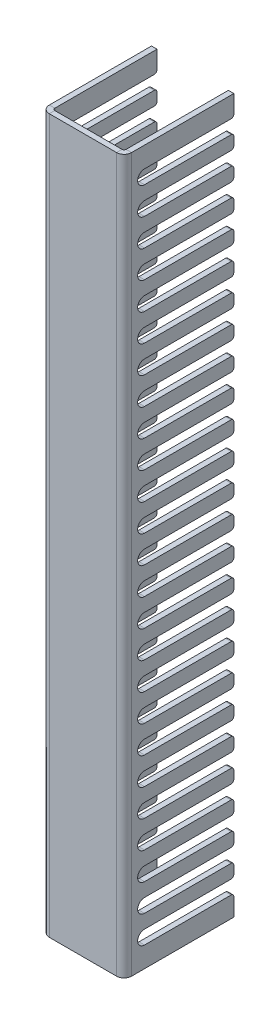
SolidWorks part; units mm, degrees
note: The reader was unsure of these and kept them because the rebuilt part matched: flange length of "边线-法兰1".
ref_plane "前视基准面" through (0, 0, 0) normal (0, 0, 1) x (1, 0, 0)
ref_plane "上视基准面" through (0, 0, 0) normal (0, 1, 0) x (1, 0, 0)
ref_plane "右视基准面" through (0, 0, 0) normal (1, 0, 0) x (0, 0, -1)
sketch "草图1" plane through (0, 0, 0) normal (0, 0, 1) x (1, 0, 0)
  line L1 (-18.0132, 35.6887) -> (11.9868, 35.6887)
  line L2 (-18.0132, 35.6887) -> (-18.0132, -224.3113)
  line L3 (-18.0132, -224.3113) -> (11.9868, -224.3113)
  line L4 (11.9868, 35.6887) -> (11.9868, -224.3113)
  dimension "D1" = 30
  dimension "D2" = 260
sheet metal parameters "钣金1" thickness 2 parameters "D1"=0.7366
base flange "基体-法兰1" sketch "草图1" thickness 2 reverse thickness direction no parameters "D1"=0.7366
edge flange "边线-法兰1" sketch "草图9" flange profiles "草图9", "草图10" flange angle 90 flange length 40 flange position material inside bend radius 0.7366 thickness 2 relief rectangular parameters "D6"=10, "D8"=1
sketch "草图9" plane through (11.9868, 0, -2) normal (1, 0, 0) x (0, -1, 0)
  line L2 (-35.6887, 0) -> (-35.6887, 38)
  line L3 (-35.6887, 38) -> (224.3113, 38)
  line L4 (224.3113, 38) -> (224.3113, 0)
  line L7 (224.3113, 0) -> (-35.6887, 0) construction
  line L8 (224.3113, 0) -> (-35.6887, 0)
sketch "草图10" plane through (-18.0132, 0, -2) normal (-1, 0, 0) x (0, 1, 0)
  line L0 (35.6887, 0) -> (-224.3113, 0) construction
  line L1 (35.6887, 0) -> (-224.3113, 0)
  line L2 (-224.3113, 0) -> (-224.3113, 38)
  line L3 (-224.3113, 38) -> (35.6887, 38)
  line L4 (35.6887, 38) -> (35.6887, 0)
bend "边线折弯1" bend radius 0.7366 bend angle 90 parameters "D5"=1
bend "边线折弯2" bend radius 0.7366 bend angle 90 parameters "D5"=2
sketch "草图11" plane through (-18.0132, 0, 0) normal (-1, 0, 0) x (0, 0, 1)
  line L0 (-7.45, 28.1887) -> (-39, 28.1887)
  line L3 (-39, 23.1887) -> (-7.45, 23.1887)
  line L4 (-40, 29.1887) -> (-40, 22.1887)
  arc A0 (-7.45, 23.1887) -> (-7.45, 28.1887) centre (-7.45, 25.6887) ccw
  arc A1 (-40, 29.1887) -> (-39, 28.1887) centre (-39, 29.1887) ccw
  arc A2 (-40, 22.1887) -> (-39, 23.1887) centre (-39, 22.1887) cw
  dimension "D1" = 10
  dimension "D4" = 1
  dimension "D5" = 1
extrude "切除-拉伸1" cut sketch "草图11" against normal blind 30 normal cut yes
pattern_linear "阵列(线性)1" count 25 spacing 10 along (0, -1, 0) of "切除-拉伸1"
flat pattern "平板型式1" [suppressed]
sketch "折弯-线1" plane through (0, 0, 0) normal (0, 0, 1) x (1, 0, 0)
  line L0 (-16.6406, 35.6887) -> (-16.6406, -224.3113) construction
  line L1 (10.6141, -224.3113) -> (10.6141, 35.6887) construction
  line L2 (-16.6406, 35.6887) -> (-16.6406, -224.3113) construction
  line L3 (10.6141, -224.3113) -> (10.6141, 35.6887) construction
sketch3d "边界框1" [suppressed]
  line L0 (49.2414, 35.6887, 0) -> (49.2414, -224.3113, 0) construction
  line L1 (-55.2679, 35.6887, 0) -> (-55.2679, -224.3113, 0) construction
  line L2 (49.2414, 35.6887, 0) -> (-55.2679, 35.6887, 0) construction
  line L3 (49.2414, -224.3113, 0) -> (-55.2679, -224.3113, 0) construction
bend of the flat pattern "展平-<边线折弯1>1"
bend of the flat pattern "展平-<边线折弯2>1"
